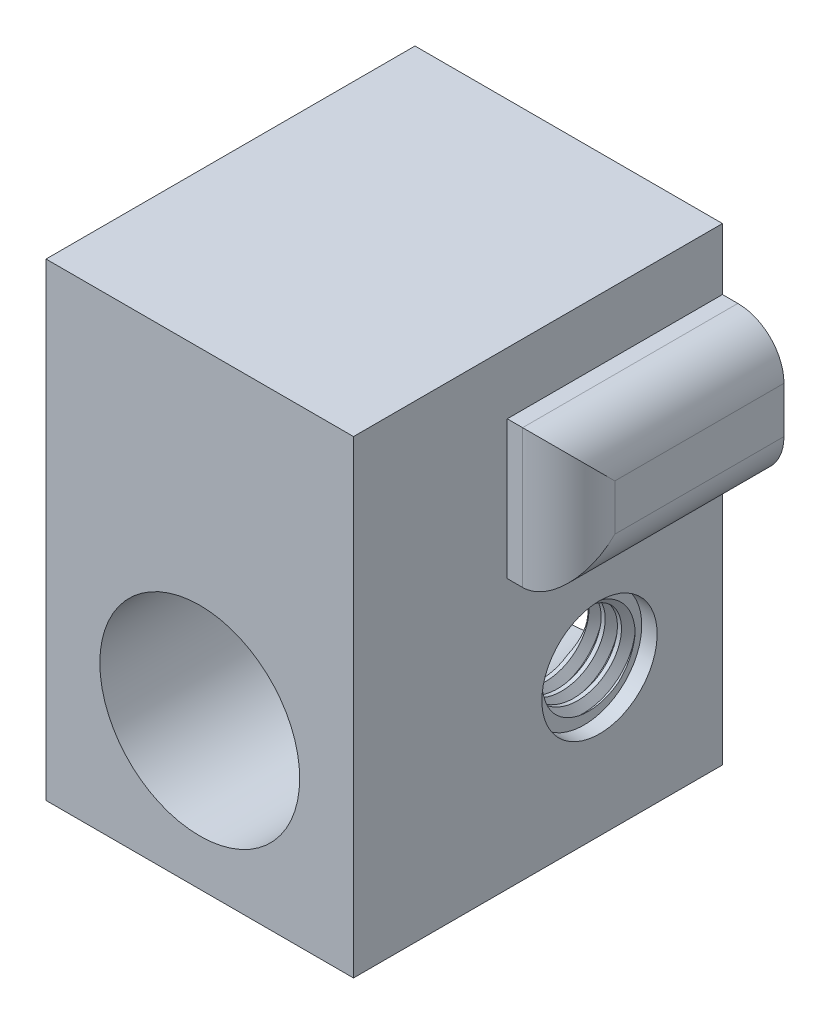
SolidWorks part; units mm, degrees
ref_plane "Front Plane" through (0, 0, 0) normal (0, 0, 1) x (1, 0, 0)
ref_plane "Top Plane" through (0, 0, 0) normal (0, 1, 0) x (1, 0, 0)
ref_plane "Right Plane" through (0, 0, 0) normal (1, 0, 0) x (0, 0, -1)
sketch "Sketch1" plane through (0, 0, 0) normal (0, 0, 1) x (1, 0, 0)
  line L1 (0, 0) -> (-20, 0)
  line L2 (0, 0) -> (0, -30.5)
  line L3 (0, -30.5) -> (-20, -30.5)
  line L4 (-20, 0) -> (-20, -30.5)
  dimension "D1" = 20
  dimension "D2" = 30.5
extrude "Boss-Extrude1" add sketch "Sketch1" along normal blind 24
sketch "Sketch2" plane through (0, 0, 24) normal (0, 0, 1) x (1, 0, 0)
  line L1 (0, 0) -> (-20, 0) construction
  line L2 (-20, -30.5) -> (0, -30.5) construction
  circle A0 centre (-10, -21) radius 6.5
  point P7 (-10, 0)
  dimension "D1" = 9.5
  dimension "D2" = 0
  dimension "D3" = 13
extrude "Cut-Extrude1" cut sketch "Sketch2" against normal blind 40
sketch "Sketch8" plane through (0, 0, 0) normal (0, 0, -1) x (-1, 0, 0)
  line L0 (0, 0) -> (20, 0) construction
  circle A0 centre (10, -10.5) radius 1.75
  point P4 (10, 0)
  dimension "D1" = 0
  dimension "D2" = 3.5
  dimension "D3" = 10.5
extrude "Cut-Extrude5" cut sketch "Sketch8" against normal blind 20
sketch "Sketch13" plane through (0, 0, 0) normal (1, 0, 0) x (0, 0, -1)
  line L0 (-24, -30.5) -> (0, -30.5) construction
  line L1 (0, -30.5) -> (0, 0) construction
  circle A0 centre (-8, -21) radius 2.75
  dimension "D1" = 9.5
  dimension "D2" = 5.5
  dimension "D3" = 8
extrude "Cut-Extrude8" cut sketch "Sketch13" against normal blind 10
thread "Thread3" pitch 1.0583 method cut profile "Thread Profile3" start angle 0, offset 0, length 10, pitch 1.0583, diameter 5.5
ref_plane "Plane3" through (0, -21, 10.75) normal (0, -1, 0) x (0, 0, 1)
sketch "Thread Profile3" plane through (0, -21, 10.75) normal (0, -1, 0) x (0, 0, 1)
  line L0 (0, 0) -> (0, 1.0583) construction
  line L1 (0, 0) -> (0.5728, 0.3307)
  line L2 (0.5728, 0.3307) -> (0.5728, 0.463)
  line L3 (0.5728, 0.463) -> (0, 0.7937)
  line L4 (0.5728, 0.3969) -> (0, 0.3969) construction
  line L11 (0, 0) -> (0, 0.7937)
  point P2 (0, 0)
  dimension "Pitch" = 1.0583
  dimension "Profile_Angle" = 60
  dimension "Profile_Land" = 0.1323
  dimension "Profile_Height" = 0.5728
sketch "Sketch16" plane through (0, 0, 0) normal (1, 0, 0) x (0, 0, -1)
  circle A0 centre (-8, -21) radius 3.75
  dimension "D1" = 7.5
extrude "Cut-Extrude9" cut sketch "Sketch16" against normal blind 1
sketch "Sketch17" plane through (0, 0, 0) normal (0, 0, -1) x (-1, 0, 0)
  line L0 (0, -30.5) -> (0, 0) construction
  line L1 (0, -4) -> (-4, -4)
  line L2 (0, -4) -> (0, -13)
  line L3 (0, -13) -> (-4, -13)
  line L4 (-4, -4) -> (-4, -13)
  line L5 (0, 0) -> (20, 0) construction
  dimension "D1" = 9
  dimension "D2" = 4
  dimension "D3" = 4
extrude "Boss-Extrude2" add sketch "Sketch17" against normal blind 14
sketch "Sketch18" plane through (0, 0, 0) normal (0, 0, -1) x (-1, 0, 0)
  line L0 (0, -4) -> (0, 0) construction
  line L1 (0, -6) -> (-2, -6)
  line L2 (0, -6) -> (0, -11)
  line L3 (0, -11) -> (-2, -11)
  line L4 (-2, -6) -> (-2, -11)
  line L5 (-4, -4) -> (-4, -13) construction
  point P6 (-2, -8.5)
  point P9 (-4, -8.5)
  dimension "D1" = 2
  dimension "D2" = 0
  dimension "D3" = 5
  dimension "D4" = 0
extrude "Cut-Extrude10" cut sketch "Sketch18" against normal blind 12
fillet "Fillet1" radius 3 3 edges at (4, -8.5, 14) (4, -4, 7) (4, -13, 7)
